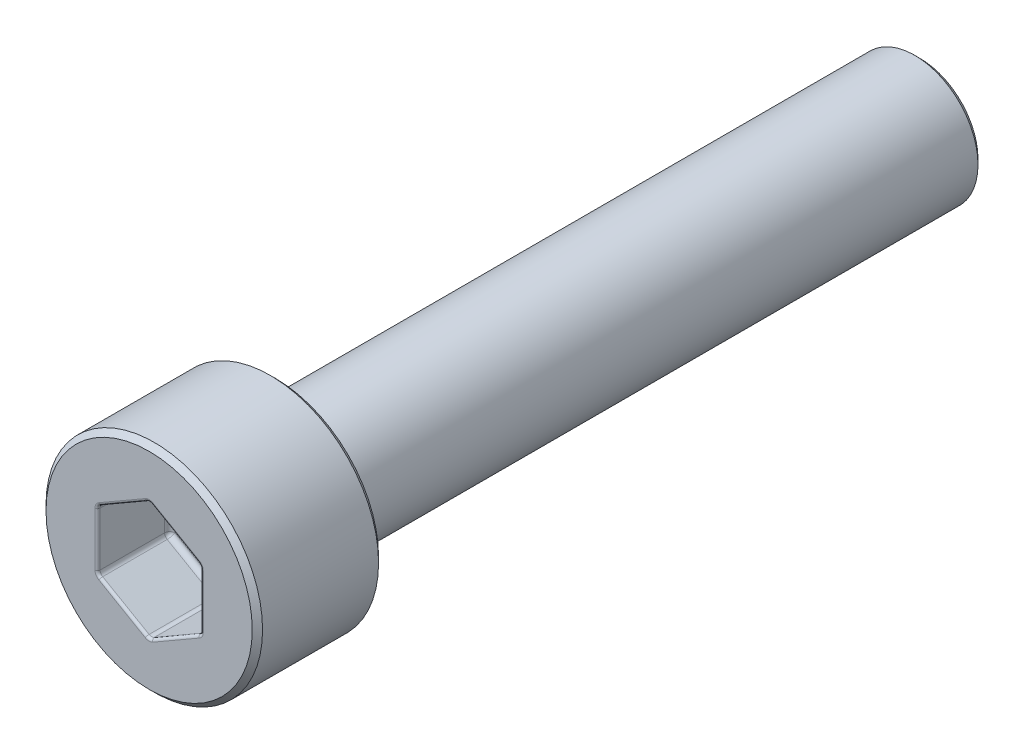
SolidWorks part; units mm, degrees
material "1.4000 (X6Cr13)"
ref_plane "Ebene vorne" through (0, 0, 0) normal (0, 0, 1) x (1, 0, 0)
ref_plane "Ebene oben" through (0, 0, 0) normal (0, 1, 0) x (1, 0, 0)
ref_plane "Ebene rechts" through (0, 0, 0) normal (1, 0, 0) x (0, 0, -1)
sketch "Skizze1" plane through (0, 0, 0) normal (1, 0, 0) x (0, 0, -1)
  line L0 (-21.9199, 0) -> (33.7608, 0) construction
  line L1 (0, 13.9907) -> (0, -9.4798) construction
  line L2 (-4.9, 0) -> (-4.9, 4.2)
  line L3 (-4.9, 4.2) -> (0, 4.2)
  line L4 (0, 4.2) -> (0, 2.45)
  line L5 (0, 2.45) -> (25, 2.45)
  line L6 (25, 2.45) -> (25, 0)
  line L7 (25, 0) -> (-4.9, 0)
  dimension "D1" = 4.9
  dimension "D2" = 4.9
  dimension "D3" = 8.4
  dimension "D4" = 25
revolve "Rotation1" add sketch "Skizze1" angle 360 about L0
sketch "Skizze2" plane through (0, 0, 4.9) normal (0, 0, 1) x (1, 0, 0)
  line L0 (0, 8.6995) -> (0, -7.3778) construction
  line L1 (2, -1.1547) -> (2, 1.1547)
  line L2 (2, 1.1547) -> (0, 2.3094)
  line L3 (0, 2.3094) -> (-2, 1.1547)
  line L4 (-2, 1.1547) -> (-2, -1.1547)
  line L5 (-2, -1.1547) -> (0, -2.3094)
  line L6 (0, -2.3094) -> (2, -1.1547)
  circle A0 centre (0, 0) radius 2 construction
  dimension "D1" = 4
extrude "Schnitt-Linear austragen1" cut sketch "Skizze2" against normal blind 2.8
chamfer "Fase1" distance 0.2 angle 45 3 edges at (4.2, 0, 4.9) (4.2, 0, 0) (2.45, 0, -25)
fillet "Verrundung1" radius 0.2 13 edges at (-1, -1.7321, 2.1) (-2, 0, 2.1) (-1, 1.7321, 2.1) (1, 1.7321, 2.1) (2, 0, 2.1) (1, -1.7321, 2.1) (-2, -1.1547, 3.5) (0, -2.3094, 3.5) (2, -1.1547, 3.5) (2, 1.1547, 3.5) (0, 2.3094, 3.5) (-2, 1.1547, 3.5) (2.45, 0, 0)
fillet "Verrundung2" radius 0.1 12 edges at (1.9732, -1.1392, 4.9) (1, -1.7321, 4.9) (0, -2.2785, 4.9) (-1, -1.7321, 4.9) (-1.9732, -1.1392, 4.9) (-2, 0, 4.9) (-1.9732, 1.1392, 4.9) (-1, 1.7321, 4.9) (0, 2.2785, 4.9) (1, 1.7321, 4.9) (1.9732, 1.1392, 4.9) (2, 0, 4.9)
ref_axis "Achse1" through (0, 0, -19.6323) along (0, 0, 1)
